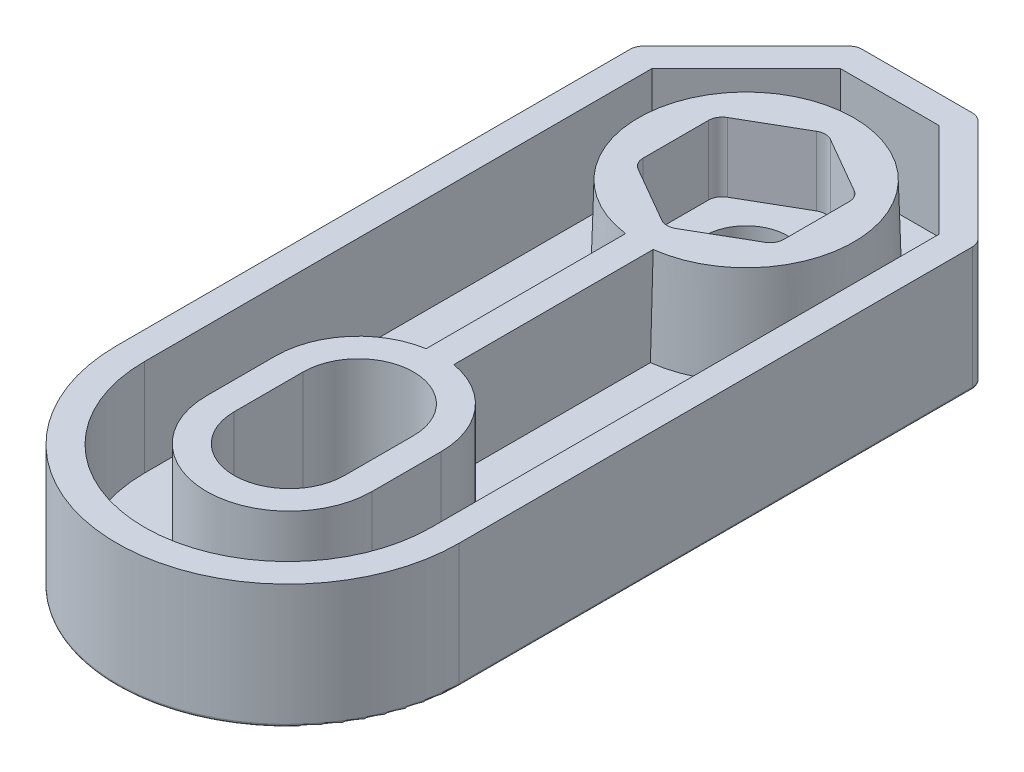
SolidWorks part; units mm, degrees
material "ABS"
ref_plane "Front Plane" through (0, 0, 0) normal (0, 0, 1) x (1, 0, 0)
ref_plane "Top Plane" through (0, 0, 0) normal (0, 1, 0) x (1, 0, 0)
ref_plane "Right Plane" through (0, 0, 0) normal (1, 0, 0) x (0, 0, -1)
sketch "BaseS" plane through (0, 0, 0) normal (0, 1, 0) x (1, 0, 0)
  line L0 (0, 18.8) -> (0, -18.8) construction
  line L1 (12.4, 18.3858) -> (12.4, -18.8)
  line L2 (-12.4, 18.3858) -> (-12.4, -18.8)
  line L3 (-12.1071, 19.0929) -> (-4.6929, 26.5071)
  line L4 (-3.9858, 26.8) -> (3.9858, 26.8)
  line L5 (4.6929, 26.5071) -> (12.1071, 19.0929)
  line L6 (0, 18.8) -> (0, 26.8) construction
  line L7 (0, -18.8) -> (0, -31.2) construction
  line L8 (12.4, 18.8) -> (-12.4, 18.8) construction
  arc A1 (-12.4, -18.8) -> (12.4, -18.8) centre (0, -18.8) ccw
  arc A2 (12.4, 18.3858) -> (12.1071, 19.0929) centre (11.4, 18.3858) ccw
  arc A3 (4.6929, 26.5071) -> (3.9858, 26.8) centre (3.9858, 25.8) ccw
  arc A4 (-3.9858, 26.8) -> (-4.6929, 26.5071) centre (-3.9858, 25.8) ccw
  arc A5 (-12.1071, 19.0929) -> (-12.4, 18.3858) centre (-11.4, 18.3858) ccw
  point P2 (0, 0)
  point P19 (4.4, 26.8)
  point P22 (-4.4, 26.8)
  dimension "Radius" = 1
  dimension "Height" = 58
  dimension "BottomWidth" = 24.8
  dimension "TopHeight" = 8
  dimension "TopWidth" = 8.8
  dimension "Angle" = 45
extrude "Base" add sketch "BaseS" along normal blind 2
sketch "WallS" plane through (0, 2, 0) normal (0, 1, 0) x (1, 0, 0)
  line L0 (10.4, -18.8) -> (10.4, 17.9716)
  line L1 (10.4, 17.9716) -> (3.5716, 24.8)
  line L2 (3.5716, 24.8) -> (-3.5716, 24.8)
  line L3 (-3.5716, 24.8) -> (-10.4, 17.9716)
  line L4 (-10.4, 17.9716) -> (-10.4, -18.8)
  line L5 (12.4, -18.8) -> (12.4, 18.3858)
  line L6 (12.1071, 19.0929) -> (4.6929, 26.5071)
  line L7 (3.9858, 26.8) -> (-3.9858, 26.8)
  line L8 (-4.6929, 26.5071) -> (-12.1071, 19.0929)
  line L9 (-12.4, 18.3858) -> (-12.4, -18.8)
  line L10 (12.4, -18.8) -> (12.4, 18.3858)
  line L11 (12.1071, 19.0929) -> (4.6929, 26.5071)
  line L12 (3.9858, 26.8) -> (-3.9858, 26.8)
  line L13 (-4.6929, 26.5071) -> (-12.1071, 19.0929)
  line L14 (-12.4, 18.3858) -> (-12.4, -18.8)
  arc A0 (10.4, 17.9716) -> (10.4, 17.9716) centre (10.4, 17.9716) ccw
  arc A1 (3.5716, 24.8) -> (3.5716, 24.8) centre (3.5716, 24.8) ccw
  arc A2 (-3.5716, 24.8) -> (-3.5716, 24.8) centre (-3.5716, 24.8) ccw
  arc A3 (-10.4, 17.9716) -> (-10.4, 17.9716) centre (-10.4, 17.9716) ccw
  arc A4 (-10.4, -18.8) -> (10.4, -18.8) centre (0, -18.8) ccw
  arc A5 (-12.4, -18.8) -> (12.4, -18.8) centre (0, -18.8) ccw
  arc A6 (12.4, 18.3858) -> (12.1071, 19.0929) centre (11.4, 18.3858) ccw
  arc A7 (4.6929, 26.5071) -> (3.9858, 26.8) centre (3.9858, 25.8) ccw
  arc A8 (-3.9858, 26.8) -> (-4.6929, 26.5071) centre (-3.9858, 25.8) ccw
  arc A9 (-12.1071, 19.0929) -> (-12.4, 18.3858) centre (-11.4, 18.3858) ccw
  arc A10 (-12.4, -18.8) -> (12.4, -18.8) centre (0, -18.8) ccw
  arc A11 (12.4, 18.3858) -> (12.1071, 19.0929) centre (11.4, 18.3858) ccw
  arc A12 (4.6929, 26.5071) -> (3.9858, 26.8) centre (3.9858, 25.8) ccw
  arc A13 (-3.9858, 26.8) -> (-4.6929, 26.5071) centre (-3.9858, 25.8) ccw
  arc A14 (-12.1071, 19.0929) -> (-12.4, 18.3858) centre (-11.4, 18.3858) ccw
  dimension "D1" = 0
  dimension "Thickness" = 2
extrude "Wall" add sketch "WallS" along normal blind 7
hole_wizard "Ø6.0 (6) Diameter Hole1" positions "Sketch3" profile "Sketch4" hole size "Ø6.0" standard "ANSI Metric" end condition through all
sketch "Sketch3" plane through (0, 0, 0) normal (0, -1, 0) x (-1, 0, 0)
  line L0 (0, 26.8) -> (0, 14.4) construction
  line L1 (-3.9858, 26.8) -> (3.9858, 26.8) construction
  point P0 (0, 14.4)
  dimension "Height" = 12.4
sketch "Sketch4" plane through (0, 0, -14.4) normal (1, 0, 0) x (0, 0, -1)
  line L0 (0, 0) -> (0, 9)
  line L1 (0, 9) -> (3, 9)
  line L2 (3, 9) -> (3, 0)
  line L5 (3, 0) -> (0, 0)
  line L11 (0, -6.35) -> (0, 107.95) construction
  dimension "Thru Hole Dia." = 6
  dimension "Thru Hole Depth" = 9
sketch "SlotS" plane through (0, 0, 0) normal (0, -1, 0) x (-1, 0, 0)
  line L0 (0, -18.7) -> (0, -13.7) construction
  line L1 (-4, -18.7) -> (-4, -13.7)
  line L2 (4, -18.7) -> (4, -13.7)
  line L3 (0, -31.2) -> (0, -18.7) construction
  arc A0 (-4, -18.7) -> (4, -18.7) centre (0, -18.7) ccw
  arc A1 (4, -13.7) -> (-4, -13.7) centre (0, -13.7) ccw
  arc A3 (-12.4, -18.8) -> (12.4, -18.8) centre (0, -18.8) ccw construction
  point P2 (0, -16.2)
  dimension "Width" = 8
  dimension "YDim" = 12.5
  dimension "Length" = 5
extrude "Slot" cut sketch "SlotS" against normal through all
sketch "SlotWallS" plane through (0, 2, 0) normal (0, 1, 0) x (1, 0, 0)
  line L1 (-4, -13.7) -> (-4, -18.7) construction
  line L2 (4, -18.7) -> (4, -13.7) construction
  line L3 (-4, -13.7) -> (-4, -18.7)
  line L4 (4, -18.7) -> (4, -13.7)
  line L5 (-6, -13.7) -> (-6, -18.7)
  line L6 (6, -18.7) -> (6, -13.7)
  arc A0 (-4, -18.7) -> (4, -18.7) centre (0, -18.7) ccw construction
  arc A1 (-6, -18.7) -> (6, -18.7) centre (0, -18.7) ccw
  arc A3 (4, -13.7) -> (-4, -13.7) centre (0, -13.7) ccw construction
  arc A4 (-4, -18.7) -> (4, -18.7) centre (0, -18.7) ccw
  arc A5 (4, -13.7) -> (-4, -13.7) centre (0, -13.7) ccw
  arc A6 (6, -13.7) -> (-6, -13.7) centre (0, -13.7) ccw
  dimension "Thickness" = 2
extrude "SlotWall" add sketch "SlotWallS" along normal up to surface (7 mm away) up to face at (0, 9, -13.177)
ref_plane "LoftedHoleWallP" through (0, 0, -14.4) normal (0, 0, 1) x (1, 0, 0)
sketch "LoftedHoleWallS" plane through (0, 0, -14.4) normal (0, 0, 1) x (1, 0, 0)
  line L0 (-3, 2) -> (-8, 2)
  line L1 (-8, 2) -> (-7.8, 9)
  line L2 (-7.8, 9) -> (-3, 9)
  line L3 (-3, 9) -> (-3, 2)
  line L4 (0, 2) -> (0, 0) construction
  line L5 (12.4, 9) -> (-12.4, 9) construction
  dimension "D1" = 8
  dimension "UpperDiaControl" = 0.2
revolve "LoftedHoleWall" add sketch "LoftedHoleWallS" angle 360 about axis through (0, 0, -14.4) along (0, -1, 0)
sketch "MidWallS" plane through (0, 2, 0) normal (0, 1, 0) x (1, 0, 0)
  line L0 (0, 6.6644) -> (0, 0) construction
  line L5 (-1, 6.6644) -> (1, 6.6644)
  line L6 (-1, 6.6644) -> (-1, -7.7839)
  line L7 (-1, -7.7839) -> (1, -7.7839)
  line L8 (1, 6.6644) -> (1, -7.7839)
  line L9 (-1, 6.6644) -> (1, -7.7839) construction
  line L10 (-1, -7.7839) -> (1, 6.6644) construction
  circle A0 centre (0, 14.4) radius 7.8 construction
  arc A1 (6, -13.7) -> (-6, -13.7) centre (0, -13.7) ccw construction
  point P0 (0, -0.5598)
  dimension "Width" = 2
extrude "MidWall" add sketch "MidWallS" along normal up to surface (7 mm away) up to face at (0, 9, -13.177)
sketch "NutProfileS" plane through (0, 9, 0) normal (0, 1, 0) x (1, 0, 0)
  line L0 (-2.09, 14.4) -> (2.09, 14.4) construction
  line L1 (0, 20.289) -> (-5.1, 17.3445)
  line L2 (-5.1, 17.3445) -> (-5.1, 11.4555)
  line L3 (-5.1, 11.4555) -> (0, 8.511)
  line L4 (0, 8.511) -> (5.1, 11.4555)
  line L5 (5.1, 11.4555) -> (5.1, 17.3445)
  line L6 (5.1, 17.3445) -> (0, 20.289)
  circle A0 centre (0, 14.4) radius 5.1 construction
  dimension "D1" = 10.2
extrude "NutProfile" cut sketch "NutProfileS" against normal blind 5
fillet "NPF" radius 1 6 edges at (-5.1, 6.5, -17.3445) (-5.1, 6.5, -11.4555) (0, 6.5, -8.511) (5.1, 6.5, -11.4555) (5.1, 6.5, -17.3445) (0, 6.5, -20.289)
fillet "BaseF" radius 0.2 15 edges at (12.4, 0, 0.2071) (12.3239, 0, -18.7685) (8.4, 0, -22.8) (4.3685, 0, -26.7239) (0, 0, -26.8) (-4.3685, 0, -26.7239) (-8.4, 0, -22.8) (-12.3239, 0, -18.7685) (-12.4, 0, 0.2071) (0, 0, 31.2) (0, 0, -17.4) (0, 0, 9.7) (4, 0, 16.2) (0, 0, 22.7) (-4, 0, 16.2)
